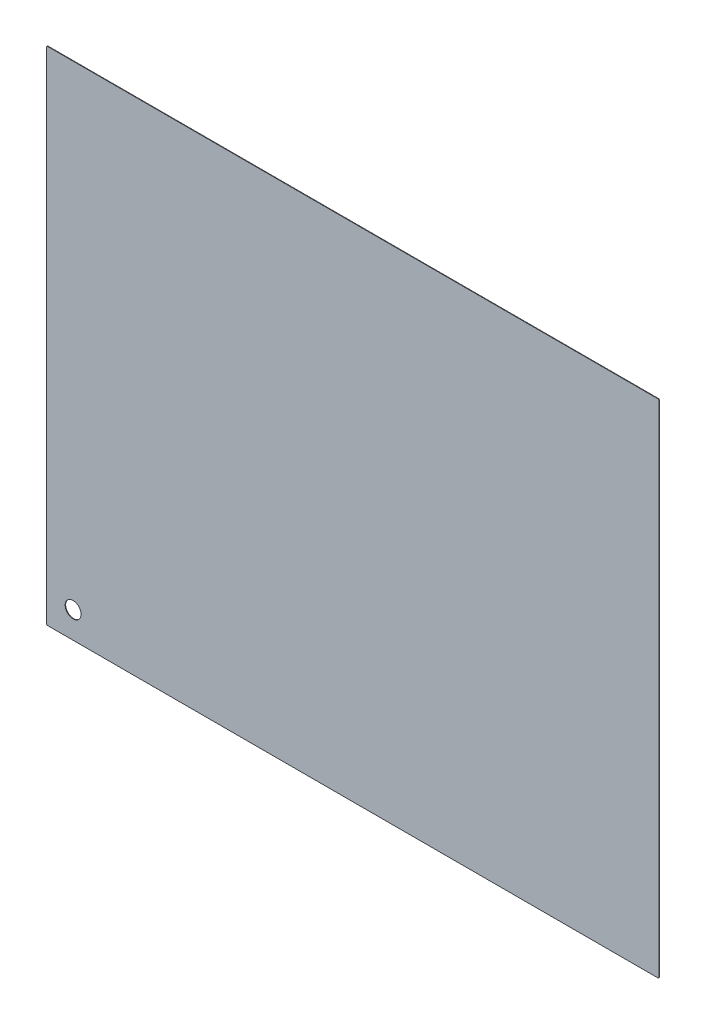
SolidWorks part; units mm, degrees
note: The reader was unsure of these and kept them because the rebuilt part matched: thickness of "Base-Flange1", "Sheet-Metal1".
ref_plane "Front Plane" through (0, 0, 0) normal (0, 0, 1) x (1, 0, 0)
ref_plane "Top Plane" through (0, 0, 0) normal (0, 1, 0) x (1, 0, 0)
ref_plane "Right Plane" through (0, 0, 0) normal (1, 0, 0) x (0, 0, -1)
sketch "Sketch1" plane through (0, 0, 0) normal (0, 0, 1) x (1, 0, 0)
  line L1 (2, 0) -> (1154, 0)
  line L2 (0, 2) -> (0, 945)
  line L3 (2, 947) -> (1154, 947)
  line L4 (1156, 2) -> (1156, 945)
  arc A0 (2, 0) -> (0, 2) centre (2, 2) cw
  arc A1 (1154, 0) -> (1156, 2) centre (1154, 2) ccw
  arc A2 (1154, 947) -> (1156, 945) centre (1154, 945) cw
  arc A3 (0, 945) -> (2, 947) centre (2, 945) cw
  circle A4 centre (50, 50) radius 15
  point P7 (0, 0)
  dimension "D3" = 2
  dimension "D4" = 30
  dimension "D5" = 50
  dimension "D6" = 50
  dimension "D1" = 1156
  dimension "D2" = 947
base flange "Base-Flange1" sketch "Sketch1" thickness 1 reverse thickness direction no parameters "D1"=1
sketch "Bend-Lines1" [suppressed] plane through (0, 0, 0) normal (0, 1, 0) x (1, 0, 0)
sketch "Bounding-Box1" [suppressed] plane through (0, 0, 0) normal (0, 1, 0) x (1, 0, 0)
sheet metal parameters "Sheet-Metal1" thickness 1 parameters "D1"=0.7366, "D7"=0.7366
flat pattern "Flat-Pattern1" [suppressed]
sketch "Bend-Lines2" plane through (0, 0, 0) normal (0, 1, 0) x (1, 0, 0)
sketch3d "Bounding-Box2" [suppressed]
  line L0 (-1.9995, 945.0006, 0) -> (1154, 945, 0) construction
  line L1 (-2, -1.9994, 0) -> (1153.9995, -2, 0) construction
  line L2 (-1.9995, 945.0006, 0) -> (-2, -1.9994, 0) construction
  line L3 (1154, 945, 0) -> (1153.9995, -2, 0) construction
